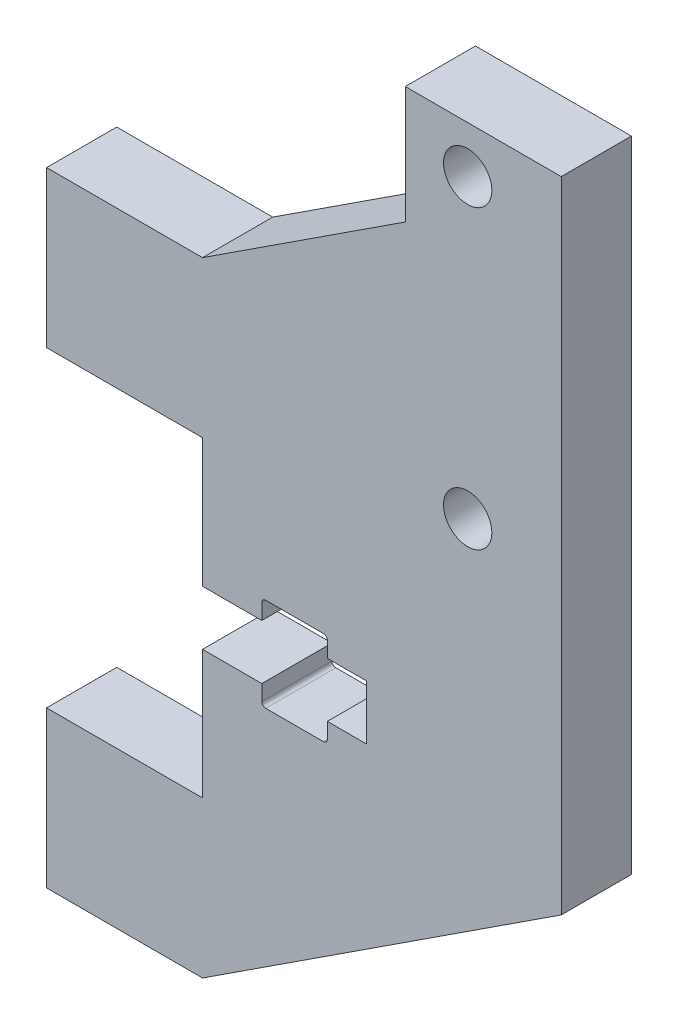
SolidWorks part; units mm, degrees
ref_plane "Front Plane" through (0, 0, 0) normal (0, 0, 1) x (1, 0, 0)
ref_plane "Top Plane" through (0, 0, 0) normal (0, 1, 0) x (1, 0, 0)
ref_plane "Right Plane" through (0, 0, 0) normal (1, 0, 0) x (0, 0, -1)
sketch "Sketch1" plane through (0, 0, 0) normal (0, 0, 1) x (1, 0, 0)
  line L0 (13, 3.4783) -> (0, -5)
  line L1 (0, -5) -> (-10, -5)
  line L2 (-10, -5) -> (-10, -15)
  line L3 (-10, -15) -> (0, -15)
  line L4 (0, -15) -> (0, -35)
  line L5 (0, -35) -> (-10, -35)
  line L6 (-10, -35) -> (-10, -45)
  line L7 (-10, -45) -> (0, -45)
  line L10 (0, -45) -> (23, -30)
  line L11 (23, -30) -> (23, 11)
  line L12 (23, 11) -> (13, 11)
  line L13 (13, 11) -> (13, 3.4783)
  line L15 (0, -5) -> (0, -45) construction
  line L16 (-10, -10) -> (0, -10) construction
  line L17 (-10, -40) -> (0, -40) construction
  line L18 (-10, -15) -> (-10, -35) construction
  line L19 (-10, -25) -> (0, -25) construction
  dimension "D2" = 10
  dimension "D3" = 10
  dimension "D4" = 10
  dimension "D5" = 15
  dimension "D8" = 10
  dimension "D10" = 13
  dimension "D6" = 15
  dimension "D7" = 16
extrude "Boss-Extrude1" add sketch "Sketch1" along normal blind 4.5
sketch "Sketch2" plane through (0, 0, 4.5) normal (0, 0, 1) x (1, 0, 0)
  line L0 (0, -25) -> (23, -25) construction
  line L1 (0, -15) -> (0, -35) construction
  line L3 (10.5, -26.75) -> (10.5, -23.25) construction
  line L4 (10.5, -23.25) -> (0, -23.25) construction
  line L5 (0, -26.75) -> (0, -23.25)
  line L6 (0, -23.25) -> (3.8, -23.25)
  line L7 (3.8, -23.25) -> (3.8, -22.25)
  line L8 (4.05, -22) -> (7.75, -22)
  line L9 (8, -22.25) -> (8, -23.25)
  line L10 (8, -23.25) -> (10.5, -23.25)
  line L11 (10.5, -23.25) -> (10.5, -26.75)
  line L12 (10.5, -26.75) -> (0, -26.75) construction
  line L13 (8, -26.75) -> (10.5, -26.75)
  line L14 (8, -27.75) -> (8, -26.75)
  line L15 (4.05, -28) -> (7.75, -28)
  line L16 (3.8, -26.75) -> (3.8, -27.75)
  line L17 (0, -26.75) -> (3.8, -26.75)
  line L18 (23, -30) -> (23, 11) construction
  arc A0 (7.75, -22) -> (8, -22.25) centre (7.75, -22.25) cw
  arc A1 (3.8, -22.25) -> (4.05, -22) centre (4.05, -22.25) cw
  arc A2 (3.8, -27.75) -> (4.05, -28) centre (4.05, -27.75) ccw
  arc A3 (7.75, -28) -> (8, -27.75) centre (7.75, -27.75) ccw
  point P15 (8, -22)
  point P18 (3.8, -22)
  point P27 (10.5, -25)
  point P29 (3.8, -28)
  point P30 (8, -28)
  dimension "D6" = 0.25
  dimension "D1" = 10.5
  dimension "D2" = 1.75
  dimension "D3" = 8
  dimension "D4" = 4.2
  dimension "D5" = 3
extrude "screw-cutout" cut sketch "Sketch2" against normal through all
sketch "Sketch3" plane through (0, 0, 4.5) normal (0, 0, 1) x (1, 0, 0)
  line L0 (17, 55) -> (17, -45) construction
  line L3 (13, 11) -> (13, 3.4783) construction
  line L5 (-10, -45) -> (0, -45) construction
  line L10 (10.5, -26.75) -> (10.5, -23.25) construction
  circle A1 centre (17, 8) radius 1.55
  circle A5 centre (17, -11) radius 1.55
  point P8 (10.5, -25)
  dimension "D4" = 3.1
  dimension "D11" = 3.1
  dimension "D6" = 4
  dimension "D12" = 19
  dimension "D2" = 14
extrude "Cut-Extrude2" cut sketch "Sketch3" against normal through all
sketch "Sketch4" [suppressed] plane through (0, 0, 4.5) normal (0, 0, 1) x (1, 0, 0)
  line L0 (17, -11) -> (17, 8) construction
  line L1 (17, -1.5) -> (13, -1.5) construction
  line L2 (13, 11) -> (13, 3.4783) construction
  line L4 (15, 2.5) -> (13, 2.5)
  line L5 (15, 2.5) -> (15, -5.5)
  line L6 (15, -5.5) -> (13, -5.5)
  line L7 (13, 2.5) -> (13, -5.5)
  line L8 (15, 2.5) -> (13, -5.5) construction
  line L9 (15, -5.5) -> (13, 2.5) construction
  circle A1 centre (17, 8) radius 1.55 construction
  circle A3 centre (17, -11) radius 1.55 construction
  point P11 (14, -1.5)
  dimension "D1" = 8
  dimension "D2" = 2
  dimension "D3" = 3
equation "\"X-ROD-SPACING\"=45"
equation "\"Y-ROD-SPACING\"=75"
equation "\"Z-ROD-SPACING\"=17.5"
equation "\"Y-BED-OFFSET\"=2"
equation "\"Y-BED-ROD-INSET\"=3.5"
equation "\"T-SLOT-NUT-FILLET-RADIUS\"=0.25"
equation "\"T-SLOT-SCREW-SHAFT-RADIUS\"=1.75"
equation "\"T-SLOT-SCREW-SHAFT-CUTOUT-LENGTH\"=10.5"
equation "\"T-SLOT-NUT-DEPTH\"=4.2"
equation "\"T-SLOT-NUT-WIDTH\"=3"
equation "\"T-SLOT-NUT-END-DISTANCE\"=8"
equation "\"ACRYLIC-THICKNESS\"=10"
equation "\"ACRYLIC-THICKNESS2\"=4.5"
equation "\"ACRYLIC-TAB-CUTOUT-SIZE\"=\"ACRYLIC-THICKNESS\"+\"ACRYLIC-TAB-TOLERANCE\"*2"
equation "\"ACRYLIC-TAB-WIDTH\"=\"ACRYLIC-THICKNESS\""
equation "\"ACRYLIC-M3-HOLE\"=3.1"
equation "\"SMOOTHROD-CAP-SCREW-DISTANCE\"=20"
equation "\"FRAME-WIDTH-INNER\"=370"
equation "\"NEMA17-HOLE-SPACING\"=31"
equation "\"NEMA17-CENTRAL-CUTOUT\"=22.5"
equation "\"Z-BRACKET-REACH\"=55"
equation "\"Z-ROD-INSET\"=16"
equation "\"TOP-BRACKET-SPACING\"=40"
equation "\"SMOOTHROD-X-LENGTH\"=350"
equation "\"SMOOTHROD-Y-LENGTH\"=350"
equation "\"SMOOTHROD-Z-LENGTH\"=350"
equation "\"SMOOTHROD-TIGHTENING-HEADROOM\"=.25"
equation "\"LEADSCREW-Z-LENGTH\"=300"
equation "\"SCREW-LENGTH-FRAME\"=\"ACRYLIC-THICKNESS\" + 10"
equation "\"SCREW-HEAD-RADIUS\"=6"
equation "\"PRINTED-X-SMOOTHROD-DIAMETER\"=8.2"
equation "\"PRINTED-X-SMOOTHROD-CUTOUT\"=10"
equation "\"PRINTED-X-BASE-HEIGHT\"=10"
equation "\"PRINTED-LM8UU-CUTOUT-SIZE\"=15.25"
equation "\"PRINTED-LM8UU-CUTOUT-LENGTH\"=24.5"
equation "\"PRINTED-X-IDLER-HEIGHT\"=16"
equation "\"PSU-MOUNTING-WIDTH\"=95"
equation "\"PSU-MOUNTING-HEIGHT\"=177"
equation "\"Y-BELT-TO-ROD-DISTANCE\"=20"
equation "\"SPOOL-HOLDER-ROD-SPACING\"=150"
equation "\"D1@Sketch1\"=\"ACRYLIC-TAB-WIDTH\""
equation "\"D2@Sketch1\"=\"ACRYLIC-TAB-WIDTH\""
equation "\"D3@Sketch1\"=\"ACRYLIC-THICKNESS\""
equation "\"D4@Sketch1\"=\"ACRYLIC-THICKNESS\""
equation "\"D1@Boss-Extrude1\"=\"ACRYLIC-THICKNESS2\""
equation "\"D1@Sketch2\"=\"T-SLOT-SCREW-SHAFT-CUTOUT-LENGTH\""
equation "\"D2@Sketch2\"=\"T-SLOT-SCREW-SHAFT-RADIUS\""
equation "\"D3@Sketch2\"=\"T-SLOT-NUT-END-DISTANCE\""
equation "\"D4@Sketch2\"=\"T-SLOT-NUT-DEPTH\""
equation "\"D5@Sketch2\"=\"T-SLOT-NUT-WIDTH\""
equation "\"D6@Sketch2\"=\"T-SLOT-NUT-FILLET-RADIUS\""
equation "\"D4@Sketch3\"=\"ACRYLIC-M3-HOLE\""
equation "\"D11@Sketch3\"=\"ACRYLIC-M3-HOLE\""
equation "\"Y-BED-SCREW-SPACING\"=209"
equation "\"Y-BED-SCREW-CUTOUT-SLOT-HEIGHT\"=2"
equation "\"ACRYLIC-TAB-TOLERANCE\"=.1"
equation "\"SCREW-LENGTH-MOTOR\"=\"ACRYLIC-THICKNESS\" + 5"
equation "\"SCREW-LENGTH-EXTRUDER\"=28"
equation "\"PRINTED-M3-HOLE\"=3.5"
equation "\"ACRYLIC-X-CARRIAGE-WIDTH\"=55"
equation "\"ACRYLIC-X-CARRIAGE-HEIGHT\"=75"
equation "\"ACRYLIC-X-CARRIAGE-LM8UU-CUTOUT-WIDTH\"=24.25"
equation "\"ACRYLIC-X-CARRIAGE-LM8UU-CUTOUT-HEIGHT\"=11.5"
equation "\"ACRYLIC-X-CARRIAGE-SCREW-SPACING-X\"=15"
equation "\"ACRYLIC-X-CARRIAGE-SCREW-SPACING-Y\"=33"
equation "\"ACRYLIC-X-CARRIAGE-CENTER-TAB-SPACING\"=14"
equation "\"ACRYLIC-X-CARRIAGE-EXTRUDER-OFFSET\"=26"
equation "\"ACRYLIC-X-CARRIAGE-EXTRUDER-ANGLE\"=90"
equation "\"ACRYLIC-X-CARRIAGE-EXTRUDER-SHELF-DEPTH\"=\"ACRYLIC-X-CARRIAGE-EXTRUDER-OFFSET\" + 28"
equation "\"ACRYLIC-X-CARRIAGE-EXTRUDER-BRACE-SPACING\"=23"
equation "\"ACRYLIC-X-CARRIAGE-EXTRUDER-BRACE-TAB-OFFSET\"=20"
equation "\"ACRYLIC-X-CARRIAGE-EXTRUDER-BRACE-HEIGHT\"=35"
equation "\"ACRYLIC-X-CARRIAGE-EXTRUDER-BRACE-SCREW-SPACING\"=22"
equation "\"ACRYLIC-X-CARRIAGE-DUAL-WIDTH-MULTIPLIER\"=1.65"
equation "\"ACRYLIC-X-CARRIAGE-DUAL-HOTEND-SPACING\"=42"
equation "\"ACRYLIC-X-CARRIAGE-DUAL-WIDTH\"=75"
equation "\"ACRYLIC-X-CARRIAGE-DUAL-HOTEND-SEPARATION\"=36"
equation "\"ACRYLIC-X-CARRIAGE-DUAL-MOUNT-PLATE-DEPTH\"=75"
equation "\"ACRYLIC-X-CARRIAGE-DUAL-MOUNT-BRACE-WIDTH\"=33"
equation "\"ACRYLIC-X-CARRIAGE-DUAL-MOUNT-SCREW-WIDTH\"=40"
equation "\"BLOWER-FAN-WIDTH\"=15"
